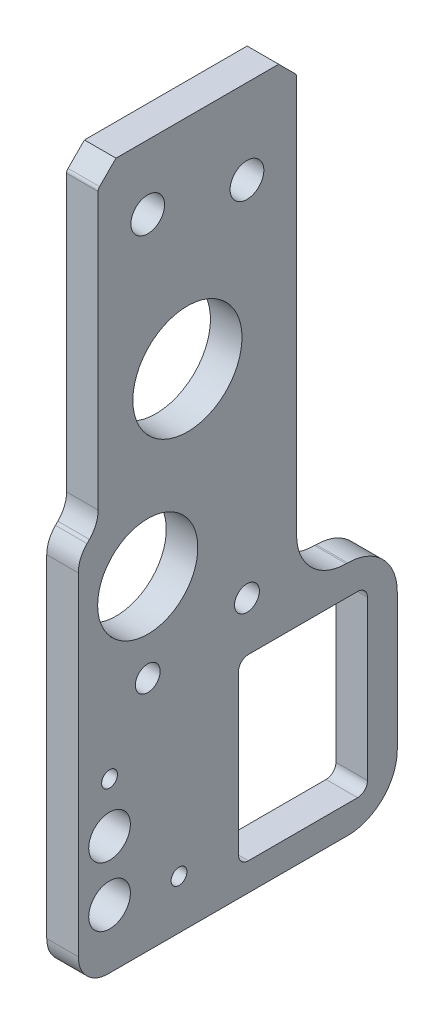
SolidWorks part; units mm, degrees
material "6061 Alloy"
ref_plane "Front Plane" through (0, 0, 0) normal (0, 0, 1) x (1, 0, 0)
ref_plane "Top Plane" through (0, 0, 0) normal (0, 1, 0) x (1, 0, 0)
ref_plane "Right Plane" through (0, 0, 0) normal (1, 0, 0) x (0, 0, -1)
sketch "Sketch1" plane through (0, 0, 0) normal (1, 0, 0) x (0, 0, -1)
  line L2 (0, 0) -> (0, 37.75)
  line L3 (0, 37.75) -> (2, 39.75)
  line L4 (2, 39.75) -> (2, 70.81)
  line L5 (2, 70.81) -> (22, 70.81)
  line L14 (-6.9356, -2) -> (62.4069, -2) construction
  line L15 (7, 37.75) -> (0, 37.75) construction
  line L23 (22, 70.81) -> (22, 23.81)
  line L31 (22, 23.81) -> (32.15, 23.81)
  line L32 (32.15, 23.81) -> (32.15, 0)
  line L33 (32.15, 0) -> (0, 0)
  line L35 (22.65, 20.81) -> (22.65, 2.81) construction
  line L36 (16.15, 20.81) -> (29.15, 20.81)
  line L37 (16.15, 20.81) -> (16.15, 2.81)
  line L38 (16.15, 2.81) -> (29.15, 2.81)
  line L39 (29.15, 20.81) -> (29.15, 2.81)
  circle A0 centre (7, 32.7) radius 5.05
  circle A1 centre (7, 64.31) radius 1.7
  circle A2 centre (17, 62.31) radius 1.7
  circle A5 centre (3.15, 5.95) radius 2.1
  circle A6 centre (3.15, 11.95) radius 2.1
  circle A9 centre (10.15, 4.95) radius 0.8
  circle A10 centre (3.15, 16.95) radius 0.8
  point P1 (7, 23.81)
  point P2 (17, 25.81)
  dimension "D11" = 10.1
  dimension "D13" = 3.4
  dimension "D17" = 15
  dimension "D21" = 2
  dimension "D33" = 4.2
  dimension "D36" = 1.6
  dimension "D4" = 18
  dimension "D5" = 13
  dimension "D22" = 15.75
  dimension "D6" = 16.15
  dimension "D7" = 5
  dimension "D8" = 2
  dimension "D9" = 2
  dimension "D10" = 47
  dimension "D12" = 34.7
  dimension "D14" = 8.5
  dimension "D15" = 6.5
  dimension "D16" = 5
  dimension "D18" = 38.11
  dimension "D19" = 3
  dimension "D20" = 3
  dimension "D23" = 7
  dimension "D24" = 20
  dimension "D25" = 5
  dimension "D28" = 2
  dimension "D30" = 6
  dimension "D32" = 3.15
  dimension "D38" = 12
extrude "Boss-Extrude1" add sketch "Sketch1" along normal blind 3.18
sketch "Sketch3" plane through (0, 0, 0) normal (-1, 0, 0) x (0, 0, 1)
  line L4 (-2, 70.81) -> (-2, 39.75) construction
  circle A0 centre (-11, 48.8109) radius 5.5
  circle A6 centre (-7, 32.7) radius 5.05 construction
  dimension "D1" = 11
  dimension "D3" = 16.6
  dimension "D2" = 9
extrude "Cut-Extrude4" cut sketch "Sketch3" against normal through all
sketch "Sketch8" [suppressed] plane through (3.18, 0, 0) normal (1, 0, 0) x (0, 0, -1)
  line L0 (2, 70.81) -> (2, 39.75) construction
  line L1 (11, 48.8109) -> (2, 48.8109) construction
  line L2 (2, 52.8109) -> (3.5, 52.8109)
  line L3 (3.5, 44.8109) -> (2, 44.8109)
  line L4 (2, 44.8109) -> (2, 52.8109)
  arc A0 (3.5, 44.8109) -> (3.5, 52.8109) centre (11, 48.8109) ccw
  circle A1 centre (7, 32.7) radius 5.05 construction
  point P11 (2, 48.8109)
  dimension "D1" = 16.6
  dimension "D2" = 17
  dimension "D3" = 9
  dimension "D4" = 8
extrude "Cut-Extrude5" [suppressed] cut sketch "Sketch8" against normal through all
fillet "Fillet2" radius 3 3 edges at (1.59, 37.75, 0) (1.59, 39.75, -2) (1.59, 0, 0)
fillet "Chamfer2" radius 1.8 2 edges at (1.59, 70.81, -22) (1.59, 70.81, -2) profile chamfer
fillet "Fillet4" radius 0.5 2 edges at (1.59, 69.01, -2) (1.59, 69.01, -22)
fillet "Fillet5" [suppressed] radius 0.3
sketch "BallRef" plane through (0, 0, 0) normal (-1, 0, 0) x (0, 0, 1)
  line L0 (-31.524, -10.56) -> (65.6624, -10.56) construction
  line L1 (-0.75, 32.7) -> (-0.75, 29.3885) construction
  line L2 (-0.75, 29.3885) -> (31.3703, 29.3885) construction
  line L3 (31.3703, 10.85) -> (31.3703, 29.3885) construction
  line L4 (1.092, -10.56) -> (-13.908, 4.44) construction
  line L5 (-13.908, 4.44) -> (-13.908, -10.56) construction
  line L6 (-13.908, -10.56) -> (1.092, -10.56) construction
  circle A0 centre (-7, 32.7) radius 6.25 construction
  circle A1 centre (9.9603, 10.85) radius 21.41 construction
  dimension "D1" = 12.5
  dimension "D2" = 42.82
  dimension "D3" = 43.26
  dimension "D4" = 45
  dimension "D5" = 15
hole_wizard "M2x0.4 Tapped Hole1" positions "3DSketch1" profile "Sketch12" tap size "M2x0.4" standard "ANSI Metric" end condition through all
sketch3d "3DSketch1"
  line L0 (3.18, 16.95, -3.15) -> (0, 16.95, -3.15) construction
  line L1 (3.18, 4.95, -10.15) -> (0, 4.95, -10.15) construction
  point P0 (0, 16.95, -3.15)
  point P4 (0, 4.95, -10.15)
sketch "Sketch12" plane through (0, 16.95, -3.15) normal (0, 1, 0) x (0, 0, 1)
  line L0 (0, 0) -> (0, 3.18)
  line L1 (0, 3.18) -> (0.8, 3.18)
  line L2 (0.8, 3.18) -> (0.8, 0)
  line L5 (0.8, 0) -> (0, 0)
  line L11 (0, -6.35) -> (0, 107.95) construction
  dimension "Thru Tap Drill Dia." = 1.6
  dimension "Thru Tap Drill Depth" = 3.18
cosmetic thread "Hole Thread3" parameters "D2"=2
cosmetic thread "Hole Thread4" parameters "D2"=2
fillet "Fillet9" radius 1 4 edges at (1.59, 2.81, -29.15) (1.59, 2.81, -16.15) (1.59, 20.81, -29.15) (1.59, 20.81, -16.15)
fillet "Fillet11" radius 5 3 edges at (1.59, 0, -32.15) (1.59, 23.81, -22) (1.59, 23.81, -32.15)
hole_wizard "M3x0.5 Tapped Hole1" positions "Sketch13" profile "Sketch14" tap size "M3x0.5" standard "ANSI Metric" end condition through all
sketch "Sketch13" plane through (3.18, 0, 0) normal (1, 0, 0) x (0, 0, -1)
  point P0 (7, 23.81)
  point P3 (17, 25.81)
sketch "Sketch14" plane through (3.18, 23.81, -7) normal (0, 1, 0) x (0, 0, -1)
  line L0 (0, 0) -> (0, 3.18)
  line L1 (0, 3.18) -> (1.25, 3.18)
  line L2 (1.25, 3.18) -> (1.25, 0)
  line L5 (1.25, 0) -> (0, 0)
  line L11 (0, -6.35) -> (0, 107.95) construction
  dimension "Thru Tap Drill Dia." = 2.5
  dimension "Thru Tap Drill Depth" = 3.18
cosmetic thread "Hole Thread5" parameters "D2"=3
cosmetic thread "Hole Thread6" parameters "D2"=3
equation "\"7.5.00mm\"=5"
